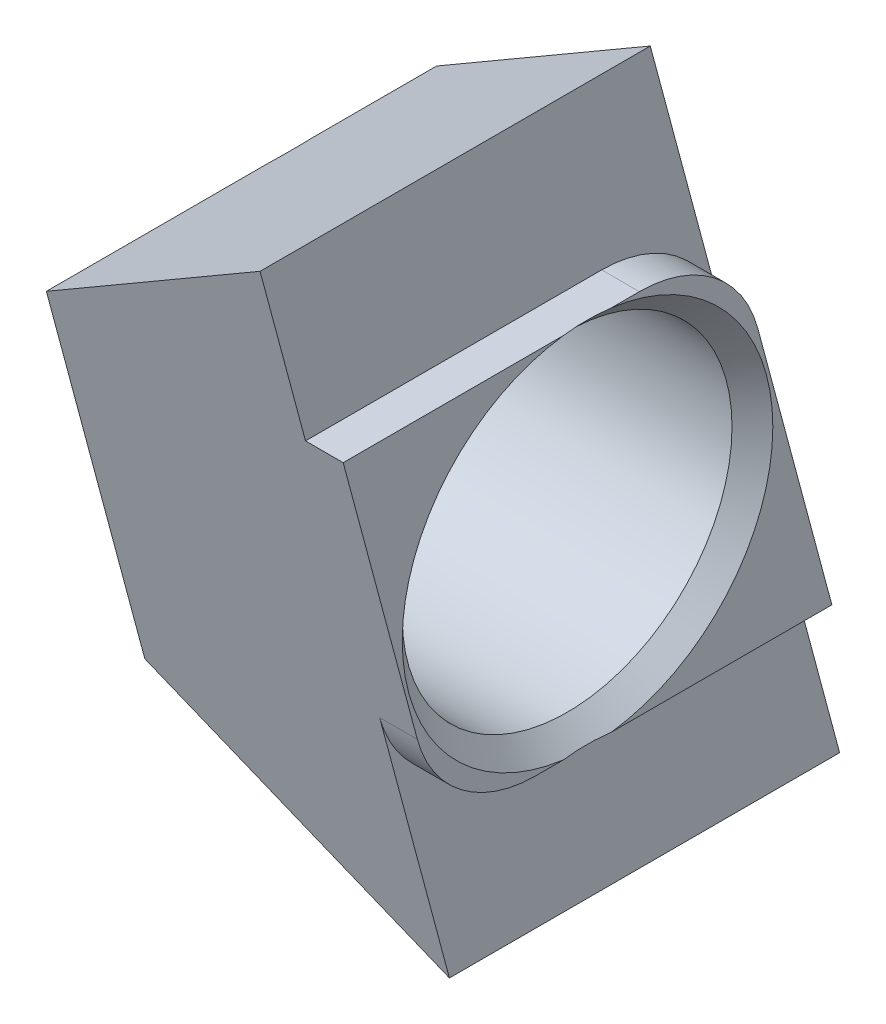
SolidWorks part; units mm, degrees
ref_plane "Piano frontale" through (0, 0, 0) normal (0, 0, 1) x (1, 0, 0)
ref_plane "Piano superiore" through (0, 0, 0) normal (0, 1, 0) x (1, 0, 0)
ref_plane "Piano destro" through (0, 0, 0) normal (1, 0, 0) x (0, 0, -1)
sketch "Sketch1" plane through (0, 0, 0) normal (1, 0, 0) x (0, 0, -1)
  line L0 (1.1011, 3.9) -> (-5.1861, 3.9)
  line L1 (-5.1861, 3.9) -> (-3.6125, -1.9729)
  line L2 (-1.1011, -3.9) -> (5.1861, -3.9)
  line L3 (5.1861, -3.9) -> (3.6125, 1.9729)
  arc A0 (-3.6125, -1.9729) -> (-1.1011, -3.9) centre (-1.1011, -1.3) ccw
  arc A1 (3.6125, 1.9729) -> (1.1011, 3.9) centre (1.1011, 1.3) ccw
extrude "Extrude1" add sketch "Sketch1" against normal blind 0.8
sketch "Sketch2" plane through (-0.8, 0, 0) normal (-1, 0, 0) x (0, 0, 1)
  line L0 (2.1315, -7.5) -> (-6.1507, -7.5)
  line L1 (-2.1315, 7.5) -> (6.1507, 7.5)
  spline S0 degree 3 poles (-2.1315, 7.5) (-3.4712, 2.5) (-4.811, -2.5) (-6.1507, -7.5) knots 0 0 0 0 1 1 1 1
  spline S1 degree 3 poles (2.1315, -7.5) (3.4712, -2.5) (4.811, 2.5) (6.1507, 7.5) knots 0 0 0 0 1 1 1 1
extrude "Extrude2" add sketch "Sketch2" along normal blind 5.5
draft "Draft1" type of draft neutral plane draft angle 33.207 faces to draft 1 face at (-3.55, 7.5, 2.0096) neutral plane through (-0.8, 0, 4.1411) neutral plane normal (1, 0, 0) reverse direction yes parameters "D1"=33.207
draft "Draft2" type of draft neutral plane draft angle 33.207 faces to draft 1 face at (-3.55, -7.5, -2.0096) neutral plane through (-0.8, 0, 4.1411) neutral plane normal (1, 0, 0) reverse direction yes parameters "D1"=33.207
hole_wizard "M6 Clearance Hole1" positions "Sketch4" profile "Sketch3" hole size "M6" standard "ANSI Metric" end condition through all
sketch "Sketch4" plane through (-6.3, 0, 0) normal (-1, 0, 0) x (0, 0, 1)
  point P0 (0, 0)
sketch "Sketch3" plane through (-6.3, 0, 0) normal (0, 1, 0) x (0, 0, 1)
  line L0 (0, 0) -> (0, 6.3)
  line L1 (0, 6.3) -> (3.5, 6.3)
  line L2 (3.5, 6.3) -> (3.5, 0)
  line L5 (3.5, 0) -> (0, 0)
  line L11 (0, -6.35) -> (0, 107.95) construction
  dimension "Thru Hole Dia." = 7
  dimension "Thru Hole Depth" = 6.3
chamfer "Chamfer1" distance 0.433 angle 45 2 edges at (0, 0, -3.5) (-6.3, 0, 3.5)
